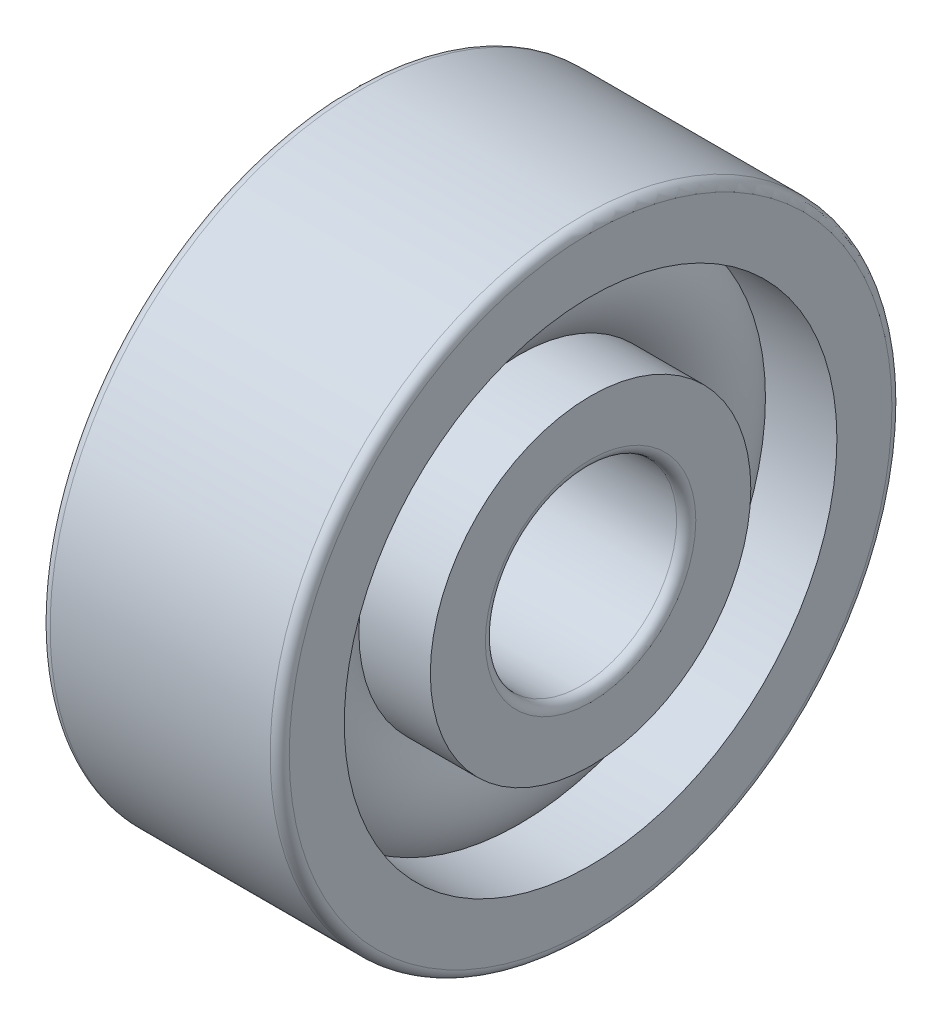
SolidWorks part; units mm, degrees
ref_plane "Plane1" through (0, 0, 0) normal (0, 0, 1) x (1, 0, 0)
ref_plane "Plane2" through (0, 0, 0) normal (0, 1, 0) x (1, 0, 0)
ref_plane "Plane3" through (0, 0, 0) normal (1, 0, 0) x (0, 0, -1)
other "Configuration Table"
sketch "Clipboard" plane through (0, 0, 0) normal (0, 0, 1) x (1, 0, 0)
  line L0 (-10, 0) -> (10, 0) construction
  line L1 (0, 0) -> (22.3471, -0.7804)
  line L2 (0, 0) -> (4.2474, 0.1483)
  line L3 (0, 0) -> (22.3471, -0.7804)
  line L4 (0, 0) -> (-22.3573, -0.3902)
  dimension "BallCLRad" = 4.25
sketch "CagSpiSke" plane through (0, 0, 0) normal (0, 0, 1) x (1, 0, 0)
  line L0 (0.135, 4.025) -> (0.135, 4.475)
  line L1 (0.135, 4.475) -> (-0.135, 4.475)
  line L2 (-0.135, 4.475) -> (-0.135, 4.025)
  line L3 (-0.135, 4.025) -> (0.135, 4.025)
  line L4 (-20.6375, 0) -> (20.6375, 0) construction
  line L5 (0, 0) -> (0, 23.7692) construction
  dimension "OD" = 8.95
  dimension "ID" = 8.05
revolve "CageSpine" add sketch "CagSpiSke" angle 0.001 about L4
ref_axis "Axis1" through (-50, 0, 0) along (1, 0, 0)
sketch "CagBalSke" plane through (0, 0, 0) normal (0, 0, 1) x (1, 0, 0)
  line L0 (-1.485, 4.25) -> (1.485, 4.25)
  line L1 (-1.905, 4.25) -> (1.905, 4.25) construction
  line L2 (-10, 0) -> (10, 0) construction
  line L3 (0, 0) -> (0, 24) construction
  arc A0 (1.485, 4.25) -> (-1.485, 4.25) centre (0, 4.25) cw
  dimension "BallCLRad" = 4.25
revolve "CageBall" [suppressed] add sketch "CagBalSke" angle 360 about L1 reverse direction yes
pattern_circular "CageBalls" [suppressed] count 2 every 180 about axis through (-50, 0, 0) along (1, 0, 0)
sketch "CagTrmODSke" plane through (0, 0, 0) normal (0, 0, 1) x (1, 0, 0)
  line L0 (1.486, 4.475) -> (1.486, 5.736)
  line L1 (1.486, 5.736) -> (-1.486, 5.736)
  line L2 (-1.486, 5.736) -> (-1.486, 4.475)
  line L3 (-1.486, 4.475) -> (1.486, 4.475)
  line L4 (-20.6375, 0) -> (20.6375, 0) construction
  line L5 (0, 0) -> (0, 25) construction
  dimension "Width" = 2.972
  dimension "ID" = 8.95
  dimension "OD" = 11.472
revolve "CageTrimOD" [suppressed] cut sketch "CagTrmODSke" angle 360 about L4 reverse direction yes
sketch "CagTrmIDSke" plane through (0, 0, 0) normal (0, 0, 1) x (1, 0, 0)
  line L0 (1.486, 2.766) -> (1.486, 4.025)
  line L1 (1.486, 4.025) -> (-1.486, 4.025)
  line L2 (-1.486, 4.025) -> (-1.486, 2.766)
  line L3 (-1.486, 2.766) -> (1.486, 2.766)
  line L4 (-20.6375, 0) -> (20.6375, 0) construction
  line L5 (0, 0) -> (0, 25) construction
  dimension "Width" = 2.972
  dimension "ID" = 5.532
  dimension "OD" = 8.05
revolve "CageTrimID" [suppressed] cut sketch "CagTrmIDSke" angle 360 about L4 reverse direction yes
sketch "BalSimSke" plane through (0, 0, 0) normal (0, 0, 1) x (1, 0, 0)
  line L0 (-10, 0) -> (10, 0) construction
  line L1 (-10, 4.25) -> (10, 4.25) construction
  line L2 (0, 0) -> (0, 23) construction
  circle A0 centre (0, 4.25) radius 1.35
  dimension "BallCLRad" = 4.25
  dimension "Ball_diameter" = 2.7
revolve "BallsSimplified" add sketch "BalSimSke" angle 360 about L0
sketch "BalDetSke" plane through (0, 0, 0) normal (0, 0, 1) x (1, 0, 0)
  line L0 (-1.35, 4.25) -> (1.35, 4.25)
  line L1 (-1.905, 4.25) -> (1.905, 4.25) construction
  line L2 (0, 0) -> (0, 25) construction
  arc A0 (1.35, 4.25) -> (-1.35, 4.25) centre (0, 4.25) cw
  dimension "BallCLRad" = 4.25
  dimension "Ball_diameter" = 2.7
revolve "BallDetailed" [suppressed] add sketch "BalDetSke" angle 360 about L1 reverse direction yes
sketch "InnRacSke" plane through (0, 0, 0) normal (0, 0, 1) x (1, 0, 0)
  line L0 (-0.9724, 3.35) -> (-2.5, 3.35)
  line L1 (-2.5, 3.35) -> (-2.5, 2.2)
  line L2 (-2.3, 2) -> (2.3, 2)
  line L3 (2.5, 2.2) -> (2.5, 3.35)
  line L4 (2.5, 3.35) -> (0.9724, 3.35)
  line L5 (-20.6375, 0) -> (20.6375, 0) construction
  line L6 (0, 0) -> (0, 30) construction
  arc A0 (-2.5, 2.2) -> (-2.3, 2) centre (-2.3, 2.2) ccw
  arc A1 (2.3, 2) -> (2.5, 2.2) centre (2.3, 2.2) ccw
  arc A2 (0.9724, 3.35) -> (-0.9724, 3.35) centre (0, 4.25) cw
  dimension "BallCLRad" = 4.25
  dimension "Fillet_radius" = 0.2
  dimension "Ball_diameter" = 2.65
  dimension "ID" = 4
  dimension "OD" = 6.7
  dimension "Width" = 5
revolve "InnerRace" add sketch "InnRacSke" angle 360 about L5 reverse direction yes
sketch "OutRacSke" plane through (0, 0, 0) normal (0, 0, 1) x (1, 0, 0)
  line L0 (-0.9724, 5.15) -> (-2.5, 5.15)
  line L1 (-2.5, 5.15) -> (-2.5, 6.3)
  line L2 (-2.3, 6.5) -> (2.3, 6.5)
  line L3 (2.5, 6.3) -> (2.5, 5.15)
  line L4 (2.5, 5.15) -> (0.9724, 5.15)
  line L5 (-20.6375, 0) -> (20.6375, 0) construction
  line L6 (0, 0) -> (0, 30) construction
  arc A0 (-2.5, 6.3) -> (-2.3, 6.5) centre (-2.3, 6.3) cw
  arc A1 (2.3, 6.5) -> (2.5, 6.3) centre (2.3, 6.3) cw
  arc A2 (0.9724, 5.15) -> (-0.9724, 5.15) centre (0, 4.25) ccw
  dimension "BallCLRad" = 4.25
  dimension "Fillet_radius" = 0.2
  dimension "Ball_diameter" = 2.65
  dimension "Width" = 5
revolve "OuterRace" add sketch "OutRacSke" angle 360 about L5 reverse direction yes
pattern_circular "BallsDetailed" [suppressed] count 2 every 180 about axis through (-50, 0, 0) along (1, 0, 0)
equation "\"BallCLRad@Clipboard\" = ( \"OD@OutRacSke\" + \"ID@InnRacSke\" ) / 4"
equation "\"BallCLRad@BalSimSke\" = \"BallCLRad@Clipboard\""
equation "\"BallCLRad@BalDetSke\" = \"BallCLRad@Clipboard\""
equation "\"BallCLRad@InnRacSke\" = \"BallCLRad@Clipboard\""
equation "\"BallCLRad@OutRacSke\" = \"BallCLRad@Clipboard\""
equation "\"Ball_diameter@InnRacSke\" = \"Ball_diameter@BalDetSke\" - 0.05"
equation "\"Ball_diameter@OutRacSke\" = \"Ball_diameter@BalDetSke\" - 0.05"
equation "\"Ball_diameter@BalSimSke\" = \"Ball_diameter@BalDetSke\""
equation "\"Width@OutRacSke\" = \"Width@InnRacSke\""
equation "\"Fillet_radius@OutRacSke\" = \"Fillet_radius@InnRacSke\""
equation "\"Max_count@Clipboard\" = int( 3.14159265 / atn(( \"Ball_diameter@BalDetSke\" / 2) / sqr( \"BallCLRad@Clipboard\"  *  \"BallCLRad@Clipboard\" - ( \"Ball_diameter@BalDetSke\" / 2) *  ( \"Ball_diameter@BalDetSke\" / 2))))"
equation "\"Max_count@Clipboard\" = ((sgn( \"Max_count@Clipboard\" - \"Count@Clipboard\" )-1)*( \"Max_count@Clipboard\" - \"Count@Clipboard\" ))/-2+ \"Count@Clipboard\""
equation "\"Count@BallsDetailed\" = int( \"Show_count@Clipboard\" ) "
equation "\"Count@BallsDetailed\" = ((sgn( \"Count@BallsDetailed\" - \"Max_count@Clipboard\" )-1)*( \"Count@BallsDetailed\" - \"Max_count@Clipboard\" ))/-2+ \"Max_count@Clipboard\""
equation "\"Count@BallsDetailed\" = ((sgn( \"Count@BallsDetailed\" - \"Min_count@Clipboard\" )+1)*( \"Count@BallsDetailed\" - \"Min_count@Clipboard\"))/2 +\"Min_count@Clipboard\""
equation "\"Angle@BallsDetailed\" = 360.0 / \"Max_count@Clipboard\""
equation "\"BallCLRad@CagBalSke\" = \"BallCLRad@Clipboard\""
equation "\"Count@CageBalls\" = \"Count@BallsDetailed\""
equation "\"Angle@CageBalls\" = \"Angle@BallsDetailed\""
equation "\"Angle@CageSpine\" =  \"Angle@CageBalls\" * ( \"Count@CageBalls\" -1 + int( \"Count@CageBalls\" / \"Max_count@Clipboard\" ) )  + 0.001 -  int( \"Count@CageBalls\" / \"Max_count@Clipboard\" ) * 0.001"
equation "\"Angle@CageSpine\" =  \"Angle@CageSpine\" * int( \"Min_count@Clipboard\" / 2) + int(1 / \"Min_count@Clipboard\")  * 0.001"
equation "\"CageWallOD@CagBalSke\" =  \"Ball_diameter@BalDetSke\" * 1.1"
equation "\"Thickness@CagSpiSke\" =  \"Ball_diameter@BalDetSke\" * 0.1"
equation "\"OD@CagTrmODSke\" = \"BallCLRad@Clipboard\" * 2 + \"CageWallOD@CagBalSke\" + 0.002"
equation "\"ID@CagTrmODSke\" = \"BallCLRad@Clipboard\" * 2 + \"Ball_diameter@BalDetSke\" / 6"
equation "\"OD@CagTrmIDSke\" = \"BallCLRad@Clipboard\" * 2 - \"Ball_diameter@BalDetSke\" / 6"
equation "\"ID@CagTrmIDSke\" = \"BallCLRad@Clipboard\" * 2 - \"CageWallOD@CagBalSke\" + 0.002"
equation "\"OD@CagSpiSke\" = \"ID@CagTrmODSke\""
equation "\"ID@CagSpiSke\" = \"OD@CagTrmIDSke\""
equation "\"Width@CagTrmODSke\" = \"CageWallOD@CagBalSke\" + 0.002"
equation "\"Width@CagTrmIDSke\" = \"CageWallOD@CagBalSke\" + 0.002"
